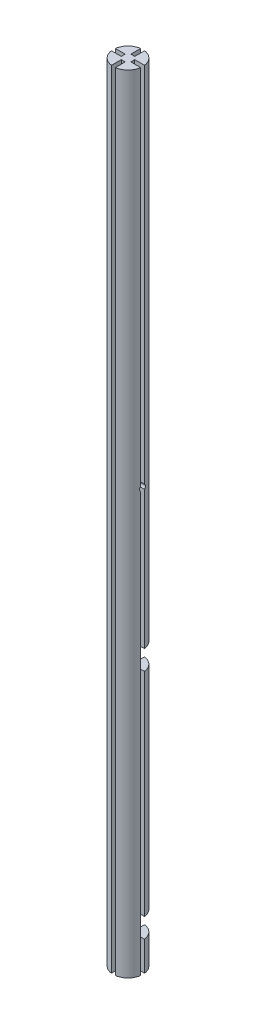
SolidWorks part; units mm, degrees
ref_plane "Front Plane" through (0, 0, 0) normal (0, 0, 1) x (1, 0, 0)
ref_plane "Top Plane" through (0, 0, 0) normal (0, 1, 0) x (1, 0, 0)
ref_plane "Right Plane" through (0, 0, 0) normal (1, 0, 0) x (0, 0, -1)
sketch "Sketch1" plane through (0, 0, 0) normal (0, 1, 0) x (1, 0, 0)
  line L5 (0, 194.153) -> (0, -244.4898) construction
  line L18 (-10, 74.3303) -> (-10, 24.3303)
  line L19 (-10, 24.3303) -> (10, 24.3303)
  line L20 (10, 74.3303) -> (10, 24.3303)
  line L21 (-29.2048, 0) -> (25.2155, 0) construction
  line L22 (74.3303, -10) -> (24.3303, -10)
  line L23 (74.3303, 10) -> (24.3303, 10)
  line L24 (24.3303, 10) -> (24.3303, -10)
  line L25 (-10, -74.3303) -> (-10, -24.3303)
  line L26 (10, -74.3303) -> (10, -24.3303)
  line L27 (10, -24.3303) -> (-10, -24.3303)
  line L28 (-74.3303, 10) -> (-24.3303, 10)
  line L29 (-74.3303, -10) -> (-24.3303, -10)
  line L30 (-24.3303, -10) -> (-24.3303, 10)
  arc A2 (-10, 74.3303) -> (-74.3303, 10) centre (0, 0) ccw
  arc A3 (-74.3303, -10) -> (-10, -74.3303) centre (0, 0) ccw
  arc A4 (10, -74.3303) -> (74.3303, -10) centre (0, 0) ccw
  arc A5 (74.3303, 10) -> (10, 74.3303) centre (0, 0) ccw
  point P1 (0, 24.3303)
  point P4 (0, 93.7498)
  point P24 (-100, 0)
  point P29 (0, 0)
  point P30 (0, 0)
  dimension "D1" = 150
  dimension "D2" = 20
  dimension "D3" = 50
  dimension "D4" = 4
extrude "Boss-Extrude2" add sketch "Sketch1" along normal blind 4000 contours A2 L28 L30 L29 A3 L25 L27 L26 A4 L22 L24 L23 A5 L20 L19 L18
sketch "Sketch2" plane through (0, 0, 0) normal (0, 1, 0) x (1, 0, 0)
  line L0 (0, 74.3303) -> (0, 0)
  line L1 (74.3303, 74.3303) -> (74.3303, 0)
  line L2 (74.3303, 74.3303) -> (0, 74.3303)
  line L3 (74.3303, 0) -> (0, 0)
extrude "Cut-Extrude1" cut sketch "Sketch2" along normal mid plane 100 from offset 200
extrude "Cut-Extrude2" cut sketch "Sketch2<2>" against normal mid plane 100 from offset 1380
sketch "Sketch2<2>" plane through (0, 0, 0) normal (0, 1, 0) x (1, 0, 0) same geometry as "Sketch2"
ref_plane "Plane1" through (74.3303, 0, 0) normal (1, 0, 0) x (0, 0, -1)
ref_plane "Plane2" through (0, 0, -74.3303) normal (0, 0, -1) x (-1, 0, 0)
sketch "Sketch3" plane through (74.3303, 0, 0) normal (1, 0, 0) x (0, 0, -1)
  circle A0 centre (0, 2143) radius 15
extrude "Cut-Extrude3" cut sketch "Sketch3" against normal up to surface (50 mm away) up to face at (24.3303, 1193.3333, -3.3333)
